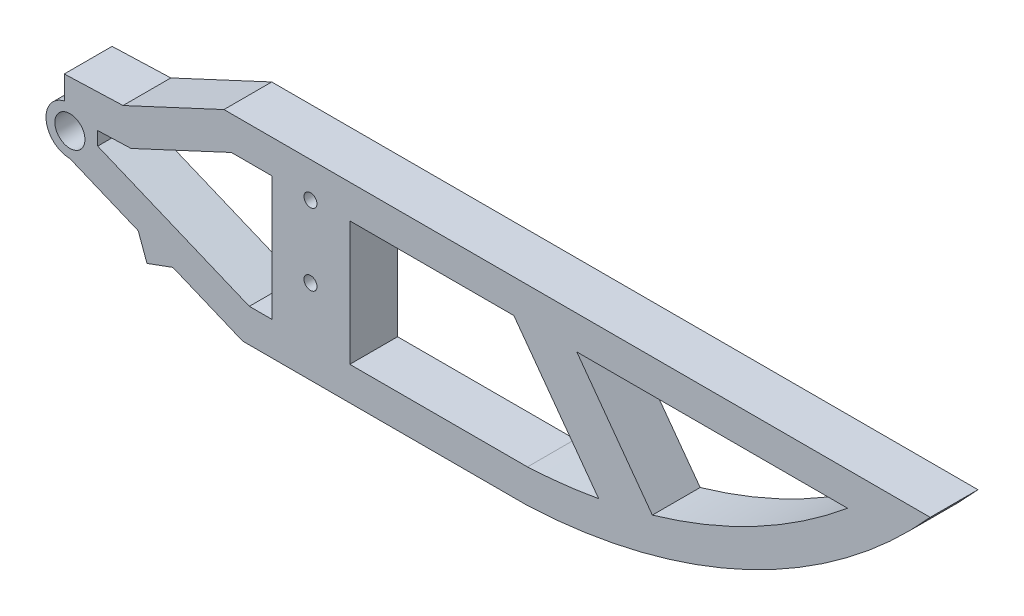
SolidWorks part; units mm, degrees
ref_plane "Front Plane" through (0, 0, 0) normal (0, 0, 1) x (1, 0, 0)
ref_plane "Top Plane" through (0, 0, 0) normal (0, 1, 0) x (1, 0, 0)
ref_plane "Right Plane" through (0, 0, 0) normal (1, 0, 0) x (0, 0, -1)
sketch "Sketch1" plane through (0, 0, 0) normal (0, 0, 1) x (1, 0, 0)
  line L1 (120.65, 25.4) -> (-120.65, 25.4)
  line L2 (120.65, 25.4) -> (120.65, -25.4)
  line L3 (120.65, -25.4) -> (-120.65, -25.4)
  line L4 (-120.65, 25.4) -> (-120.65, -25.4)
  line L5 (120.65, 25.4) -> (-120.65, -25.4) construction
  line L6 (120.65, -25.4) -> (-120.65, 25.4) construction
  point P0 (0, 0)
  dimension "D1" = 241.3
  dimension "D2" = 50.8
extrude "Boss-Extrude1" add sketch "Sketch1" along normal blind 12.7
sketch "Sketch3" plane through (0, 0, 12.7) normal (0, 0, 1) x (1, 0, 0)
  line L0 (0, 0) -> (-120.65, 0) construction
  line L1 (-120.65, 25.4) -> (-120.65, -25.4) construction
  circle A0 centre (-107.95, 0) radius 4
  dimension "D2" = 8
  dimension "D1" = 12.7
extrude "Cut-Extrude1" cut sketch "Sketch3" against normal through all
sketch "Sketch5" plane through (0, 0, 12.7) normal (0, 0, 1) x (1, 0, 0)
  line L0 (-120.65, -25.4) -> (120.65, -25.4) construction
  line L1 (-107.95, -6.35) -> (-62.0461, -25.4)
  line L2 (-107.95, 6.35) -> (-67.0151, 25.4)
  line L3 (120.65, 25.4) -> (-120.65, 25.4) construction
  line L4 (-67.0151, 25.4) -> (-120.65, 25.4)
  line L5 (-120.65, 25.4) -> (-120.65, -25.4)
  line L6 (-120.65, -25.4) -> (-62.0461, -25.4)
  line L7 (120.65, 25.4) -> (120.65, -25.4)
  line L8 (120.65, -25.4) -> (0, -25.4)
  arc A0 (0, -25.4) -> (120.65, 25.4) centre (6.9175, 126.8429) ccw
  arc A2 (-107.95, 6.35) -> (-107.95, -6.35) centre (-107.95, 0) ccw
  line M3 (-120.65, 25.4) -> (-120.65, -25.4)
  line M4 (-120.65, -25.4) -> (120.65, -25.4)
  line M5 (120.65, -25.4) -> (120.65, 25.4)
  line M6 (120.65, 25.4) -> (-120.65, 25.4)
  dimension "D1" = 152.4
  dimension "D2" = 12.7
extrude "Cut-Extrude2" cut sketch "Sketch5" against normal through all contours A2 L2 L1 M6 M3 M4 | A0 L8 M5 region at (-85.2953, -16.5913, 12.7) region at (93.5193, -10.6939, 12.7)
sketch "Sketch6" plane through (0, 0, 12.7) normal (0, 0, 1) x (1, 0, 0)
  line L0 (-107.95, 0) -> (91.396, 0) construction
  arc A0 (13.8349, -25.4) -> (120.65, 25.4) centre (6.9175, 126.8429) ccw construction
  circle A1 centre (19.05, 0) radius 3.1347
  dimension "D1" = 127
sketch "Sketch7" plane through (0, 0, 0) normal (0, 0, -1) x (-1, 0, 0)
  line L0 (44.0204, -2.9977) -> (44.0204, 16.0523) construction
  point P3 (44.0204, -2.9977)
  point P4 (44.0204, 16.0523)
  dimension "D1" = 19.05
sketch "Sketch8" plane through (0, 0, 0) normal (0, 0, -1) x (-1, 0, 0)
  point P0 (44.0204, 16.0523)
  point P3 (44.0204, -2.9977)
hole_wizard "Tap Drill for #8-32 Tap1" positions "Sketch8" profile "Sketch9" hole size "#8-32" standard "ANSI Inch" end condition through all
sketch "Sketch9" plane through (-44.0204, 16.0523, 0) normal (1, 0, 0) x (0, 1, 0)
  line L0 (0, 0) -> (0, 12.7)
  line L1 (0, 12.7) -> (1.7272, 12.7)
  line L2 (1.7272, 12.7) -> (1.7272, 0)
  line L5 (1.7272, 0) -> (0, 0)
  line L11 (0, -6.35) -> (0, 107.95) construction
  dimension "Thru Hole Dia." = 3.4544
  dimension "Thru Hole Depth" = 12.7
ref_plane "Plane1" through (-114.3, 0, 0) normal (-1, 0, 0) x (0, 0, 1)
sketch "Sketch10" plane through (-114.3, 0, 0) normal (-1, 0, 0) x (0, 0, 1)
  line L0 (0, 0) -> (12.7, 0) construction
  line L1 (12.7, -3.1347) -> (12.7, 3.1347) construction
  circle A0 centre (6.0894, 0) radius 1.905
  dimension "D1" = 3.81
extrude "Cut-Extrude3" cut sketch "Sketch10" against normal blind 5.08
sketch "Sketch11" plane through (0, 0, 12.7) normal (0, 0, 1) x (1, 0, 0)
  line L0 (-93.8249, 12.9234) -> (-109.4459, 12.9234) construction
  line L1 (-107.95, 6.35) -> (-67.0151, 25.4) construction
  line L2 (-109.4459, 12.9234) -> (-109.4459, 5.6538) construction
  line L3 (-93.8249, 12.9234) -> (-109.4459, 5.6538)
  line L4 (-93.8249, 12.9234) -> (-109.4459, 12.3779)
  line L5 (-109.4459, 12.3779) -> (-109.4459, 5.6538)
  circle A1 centre (-107.95, 0) radius 4 construction
  dimension "D1" = 15.621
  dimension "D2" = 5.6538
  dimension "D3" = 178
extrude "Boss-Extrude2" add sketch "Sketch11" against normal up to surface (12.7 mm away) up to face at (-45.7476, 16.0523, 0)
sketch "Sketch12" plane through (0, 0, 12.7) normal (0, 0, 1) x (1, 0, 0)
  line L1 (10.0217, 16.51) -> (-33.5733, 16.51)
  line L24 (-33.5733, 16.51) -> (-33.5733, -16.51)
  line L25 (-54.2244, 16.51) -> (-54.2244, -16.51)
  line L26 (-54.2244, 16.51) -> (-65.0478, 16.51)
  line L27 (-33.5733, -16.51) -> (13.63, -16.51)
  line L28 (10.0217, 16.51) -> (32.5572, -14.3581)
  line L29 (26.7339, 16.51) -> (46.8231, -11.0072)
  line L30 (-100.5559, 3.793) -> (-100.5559, 0.2066)
  line L31 (-100.5559, 0.2066) -> (-60.2747, -16.51)
  line L32 (-60.2747, -16.51) -> (13.63, -16.51)
  line L33 (98.6876, 16.51) -> (-65.0478, 16.51)
  line L34 (-65.0478, 16.51) -> (-91.7106, 4.1018)
  line L35 (-91.7106, 4.1018) -> (-100.5559, 3.793)
  line L36 (-100.5559, 3.793) -> (-100.5559, 0.2066)
  line L37 (-100.5559, 0.2066) -> (-60.2747, -16.51)
  line L38 (-60.2747, -16.51) -> (-54.2244, -16.51)
  line L39 (98.6876, 16.51) -> (26.7339, 16.51)
  line L40 (-65.0478, 16.51) -> (-91.7106, 4.1018)
  line L41 (-91.7106, 4.1018) -> (-100.5559, 3.793)
  arc A0 (46.8231, -11.0072) -> (98.6876, 16.51) centre (6.9175, 126.8429) ccw
  arc A10 (13.63, -16.51) -> (98.6876, 16.51) centre (6.9175, 126.8429) ccw
  arc A11 (13.63, -16.51) -> (32.5572, -14.3581) centre (6.9175, 126.8429) ccw
  dimension "D1" = 8.89
extrude "Cut-Extrude4" cut sketch "Sketch12" against normal through all
sketch "Sketch13" plane through (0, 0, 12.7) normal (0, 0, 1) x (1, 0, 0)
  line L0 (-80.575, -17.7106) -> (-87.4623, -20.236)
  line L1 (-107.95, -6.35) -> (-62.0461, -25.4) construction
  line L2 (-87.4623, -20.236) -> (-89.7908, -13.886)
  line L4 (-80.575, -17.7106) -> (-89.7908, -13.886)
  circle A0 centre (-107.95, 0) radius 4 construction
  dimension "D1" = 90
  dimension "D2" = 6.35
  dimension "D3" = 22.86
extrude "Boss-Extrude3" add sketch "Sketch13" against normal up to surface (12.7 mm away) up to face at (57.8889, 6.444, 0)
